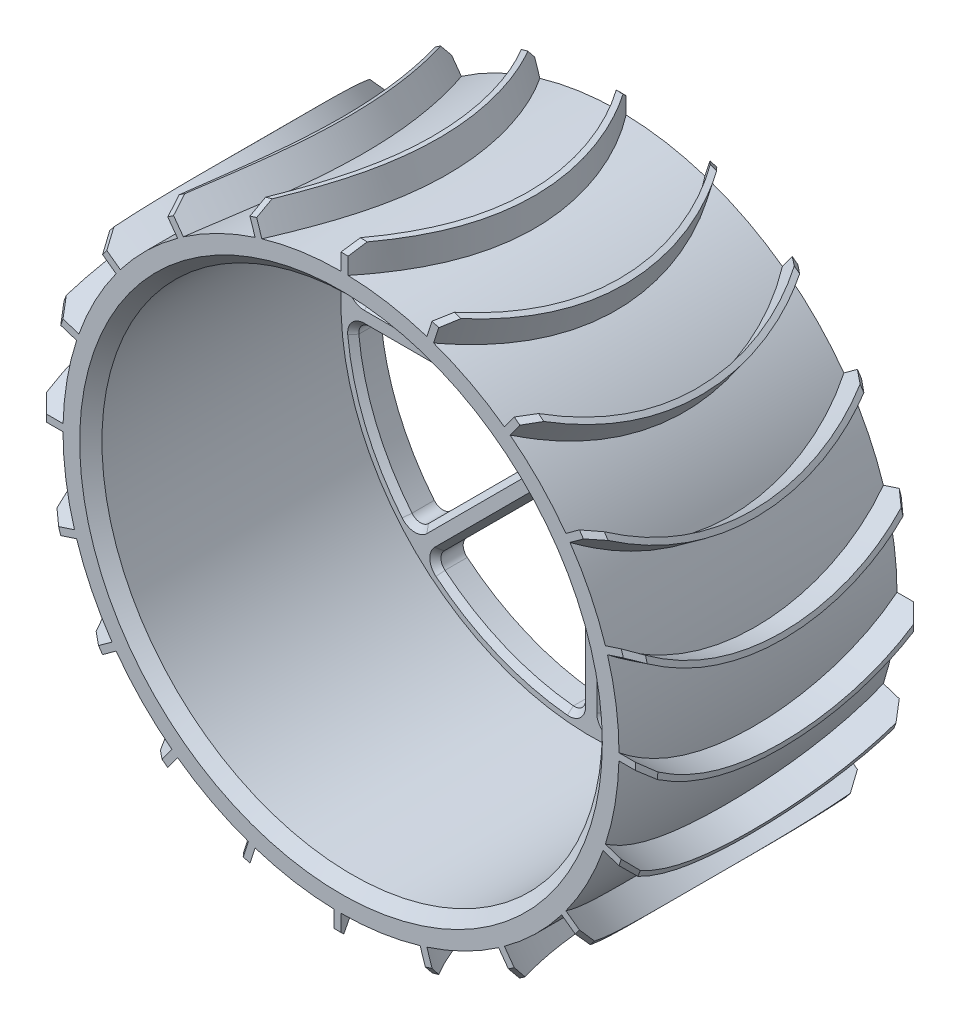
SolidWorks part; units mm, degrees
note: '?' marks a value the reader was unsure of. The reader was unsure of these and kept them because the rebuilt part matched: shared geometry of "Sketch4<3>".
ref_plane "Front Plane" through (0, 0, 0) normal (0, 0, 1) x (1, 0, 0)
ref_plane "Top Plane" through (0, 0, 0) normal (0, 1, 0) x (1, 0, 0)
ref_plane "Right Plane" through (0, 0, 0) normal (1, 0, 0) x (0, 0, -1)
ref_axis "X" through (-88.99, 0, 0) along (1, 0, 0)?
ref_axis "Y" through (0, 55, 0) along (0, -1, 0)?
ref_axis "Z" through (0, 0, -88.99) along (0, 0, 1)?
sketch "Sketch1" plane through (0, 0, 0) normal (0, 0, 1) x (1, 0, 0)
  circle A0 centre (0, 0) radius 50
  dimension "D1" = 100
extrude "Boss-Extrude1" add sketch "Sketch1" along normal mid plane 50
sketch "Sketch2" plane through (0, 0, 0) normal (0, 0, 1) x (1, 0, 0)
  line L1 (5.5, 5.5) -> (-5.5, 5.5) construction
  line L2 (5.5, 5.5) -> (5.5, -5.5) construction
  line L3 (5.5, -5.5) -> (-5.5, -5.5) construction
  line L4 (-5.5, 5.5) -> (-5.5, -5.5) construction
  line L5 (5.5, 5.5) -> (-5.5, -5.5) construction
  line L6 (5.5, -5.5) -> (-5.5, 5.5) construction
  circle A0 centre (5.5, 5.5) radius 1.6
  circle A1 centre (-5.5, 5.5) radius 1.6
  circle A2 centre (-5.5, -5.5) radius 1.6
  circle A3 centre (5.5, -5.5) radius 1.6
  circle A4 centre (0, 0) radius 2.5
  point P0 (0, 0)
  dimension "D2" = 3.2
  dimension "6" = 5
  dimension "D1" = 11
sketch "Sketch3" plane through (0, 0, 0) normal (0, 1, 0) x (1, 0, 0)
  line L0 (0, 25) -> (0, -25) construction
  line L1 (0, 25) -> (1.2712, 25)
  line L2 (0, -25) -> (1.2712, -25)
  arc A0 (0, 25) -> (0, -25) centre (-31.225, 0) cw
  arc A1 (1.2712, 25) -> (1.2712, -25) centre (-31.225, 0) cw
  point P10 (0, 0)
  dimension "D1" = 1
  dimension "D2" = 50
  dimension "D3" = 40
extrude "Boss-Extrude2" add sketch "Sketch3" along normal offset from surface (55 mm away) 5 contours A0 L2 A1 L1
chamfer "Chamfer1" distance 2 angle 45 2 edges at (0.6356, 54.9963, -25) (0.6356, 54.9963, 25)
pattern_circular "CirPattern1" count 20 over 360 about axis through (0, 0, 0) along (0, 0, 1) of "Boss-Extrude2", "Chamfer1"
sketch "Sketch4" plane through (0, 0, 0) normal (0, 0, 1) x (1, 0, 0)
  line L0 (0, 45) -> (0, 0) construction
  line L1 (-2, 40.8044) -> (-2, 14.4853)
  line L2 (0, 0) -> (-31.8198, 31.8198) construction
  line L3 (-8.8284, 11.6569) -> (-27.4389, 30.2673)
  arc A1 (-8.8284, 11.6569) -> (-2, 14.4853) centre (-6, 14.4853) ccw
  circle A2 centre (0, 0) radius 45
  circle A3 centre (0, 0) radius 45
  arc A4 (-27.2941, 33.2269) -> (-4.1951, 42.7949) centre (0, 0) cw
  arc A5 (-2, 40.8044) -> (-4.1951, 42.7949) centre (-4, 40.8044) ccw
  arc A6 (-27.2941, 33.2269) -> (-27.4389, 30.2673) centre (-26.0246, 31.6815) ccw
  dimension "D3" = 4
  dimension "D6" = 2
  dimension "D7" = 2
  dimension "D2" = 45
  dimension "D4" = 4
  dimension "D5" = 4
  dimension "D1" = 5
extrude "Cut-Extrude1" cut sketch "Sketch4" along normal through all and the other way offset from surface (20 mm away) 5 contours A3 other way up to face at (0, 0, -25)
extrude "Cut-Extrude2" cut sketch "Sketch4<3>" against normal through all contours A4 A6 L3 A1 L1 A5
sketch "Sketch4<3>" plane through (0, 0, 0) normal (0, 0, 1) x (1, 0, 0) same geometry as "Sketch4"
chamfer "Chamfer2" distance 1 angle 45 6 edges at (-28.0223, 31.7792, -20) (-16.4554, 39.7268, -20) (-18.1336, 20.9621, -20) (-2.6565, 42.286, -20) (-4.4693, 10.7898, -20) (-2, 27.6448, -20)
pattern_circular "CirPattern2" count 8 over 360 about axis through (0, 0, 0) along (0, 0, 1) of "Cut-Extrude2", "Chamfer2"
extrude "Cut-Extrude3" cut sketch "Sketch2" against normal through all
chamfer "Chamfer3" distance 2 angle 45 1 edges at (45, 0, 25)
chamfer "Chamfer4" distance 1 angle 45 1 edges at (2.5, 0, -20)
mirror "Mirror1" [suppressed] about plane through (0, 0, 0) normal (0, 0, 1)
delete or keep bodies "Body-Delete/Keep 1" [suppressed] bodies 108
